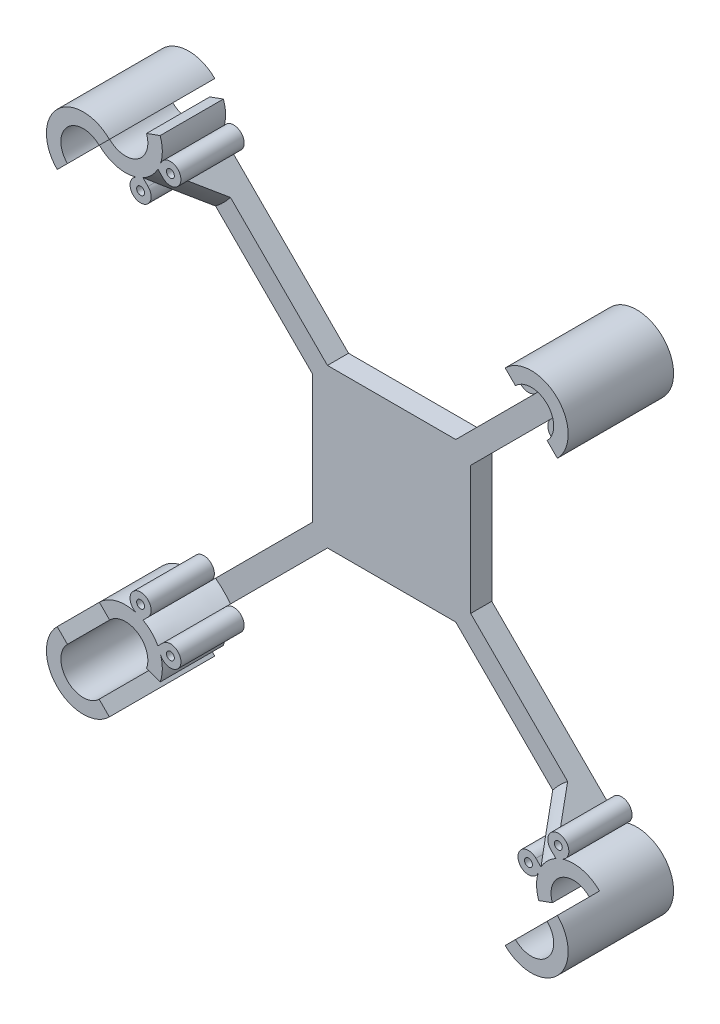
SolidWorks part; units mm, degrees
material "ABS"
ref_plane "Plano frontal" through (0, 0, 0) normal (0, 0, 1) x (1, 0, 0)
ref_plane "Plano superior" through (0, 0, 0) normal (0, 1, 0) x (1, 0, 0)
ref_plane "Plano direito" through (0, 0, 0) normal (1, 0, 0) x (0, 0, -1)
sketch "Esboço1" plane through (0, 0, 0) normal (0, 0, 1) x (1, 0, 0)
  line L0 (0, 0) -> (42.5, 42.5) construction
  line L1 (38.5063, 43.9536) -> (35.9222, 44.8941)
  line L2 (12.1716, 15) -> (36.3424, 39.1708)
  line L3 (-12.1716, 15) -> (12.1716, 15)
  line L4 (15, -12.1716) -> (15, 12.1716)
  line L5 (-1.4142, 1.4142) -> (41.0858, 43.9142) construction
  line L6 (0, 0) -> (-42.5, 42.5) construction
  line L7 (0, -45.0528) -> (0, 45.0528) construction
  line L8 (-57.1727, 0) -> (57.1727, 0) construction
  line L9 (15, 12.1716) -> (39.1708, 36.3424)
  line L10 (37.5503, 47.4497) -> (39.4948, 45.5052)
  line L11 (-37.5503, 47.4497) -> (-39.4948, 45.5052)
  line L12 (-15, 12.1716) -> (-39.1708, 36.3424)
  line L13 (-15, -12.1716) -> (-15, 12.1716)
  line L14 (-12.1716, 15) -> (-36.3424, 39.1708)
  line L15 (-38.5063, 43.9536) -> (-35.9222, 44.8941)
  line L16 (0, 0) -> (-42.5, -42.5) construction
  line L17 (0, 0) -> (42.5, -42.5) construction
  line L18 (-38.5063, -43.9536) -> (-35.9222, -44.8941)
  line L19 (-12.1716, -15) -> (-36.3424, -39.1708)
  line L20 (-15, -12.1716) -> (-39.1708, -36.3424)
  line L21 (-37.5503, -47.4497) -> (-39.4948, -45.5052)
  line L22 (37.5503, -47.4497) -> (39.4948, -45.5052)
  line L23 (15, -12.1716) -> (39.1708, -36.3424)
  line L24 (-12.1716, -15) -> (12.1716, -15)
  line L25 (12.1716, -15) -> (36.3424, -39.1708)
  line L26 (38.5063, -43.9536) -> (35.9222, -44.8941)
  line L27 (42.5, 42.5) -> (31.5501, 42.5) construction
  arc A0 (38.5063, 43.9536) -> (39.4948, 45.5052) centre (42.5, 42.5) ccw
  arc A1 (36.3424, 39.1708) -> (37.5503, 47.4497) centre (42.5, 42.5) ccw
  arc A2 (35.9222, 44.8941) -> (36.3424, 39.1708) centre (42.5, 42.5) ccw
  arc A3 (-35.9222, 44.8941) -> (-36.3424, 39.1708) centre (-42.5, 42.5) cw
  arc A4 (-36.3424, 39.1708) -> (-37.5503, 47.4497) centre (-42.5, 42.5) cw
  arc A5 (-38.5063, 43.9536) -> (-39.4948, 45.5052) centre (-42.5, 42.5) cw
  arc A6 (-38.5063, -43.9536) -> (-39.4948, -45.5052) centre (-42.5, -42.5) ccw
  arc A7 (-36.3424, -39.1708) -> (-37.5503, -47.4497) centre (-42.5, -42.5) ccw
  arc A8 (-35.9222, -44.8941) -> (-36.3424, -39.1708) centre (-42.5, -42.5) ccw
  arc A9 (35.9222, -44.8941) -> (36.3424, -39.1708) centre (42.5, -42.5) cw
  arc A10 (36.3424, -39.1708) -> (37.5503, -47.4497) centre (42.5, -42.5) cw
  arc A11 (38.5063, -43.9536) -> (39.4948, -45.5052) centre (42.5, -42.5) cw
  point P0 (0, 0)
  point P29 (0, 15)
  point P46 (-15, 0)
  point P47 (15, 0)
  point P48 (0, -15)
  dimension "D2" = 14
  dimension "D3" = 8.5
  dimension "D1" = 30
  dimension "D4" = 85
  dimension "D5" = 30
  dimension "D7" = 45
  dimension "D8" = 25
  dimension "D9" = 2
  dimension "D10" = 20
  dimension "D6" = 2
extrude "Ressalto-extrusão1" add sketch "Esboço1" along normal blind 4 contours L25 A10 L23 L4 L9 A1 L2 L3 L14 A4 L12 L13 L20 A7 L19 L24 region at (0, 0, 0)
extrude "Ressalto-extrusão2" add sketch "Esboço1<4>" along normal blind 20 contours L15 A5 L11 A4 A3 | A1 L10 A0 L1 A2 | A9 L26 A11 L22 A10 | A8 L18 A6 L21 A7 region at (-37.6903, 37.6903, 0)
sketch "Esboço1<4>" plane through (0, 0, 0) normal (0, 0, 1) x (1, 0, 0) same geometry as "Esboço1"
chamfer "Chanfro1" distance 8 angle 45 4 edges at (37.5503, -37.5503, 4) (37.5503, 37.5503, 4) (-37.5503, 37.5503, 4) (-37.5503, -37.5503, 4)
sketch "Esboço2" plane through (0, 0, 20) normal (0, 0, 1) x (1, 0, 0)
  line L0 (85, 0) -> (0, 85)
  line L1 (85, 0) -> (0, -85)
  line L2 (0, 85) -> (-85, 0)
  line L3 (0, -85) -> (-85, 0)
  line L4 (85, 0) -> (-85, 0) construction
  line L5 (0, 85) -> (0, -85) construction
  arc A0 (-39.4948, 45.5052) -> (-38.5063, 43.9536) centre (-42.5, 42.5) ccw construction
  arc A1 (-38.5063, -43.9536) -> (-39.4948, -45.5052) centre (-42.5, -42.5) ccw construction
  point P1 (0, 0)
  point P11 (-42.5, 42.5)
  point P12 (-42.5, -42.5)
extrude "Corte-extrusão1" cut sketch "Esboço2" against normal blind 8
sketch "Esboço3" plane through (0, 0, 0) normal (0, 0, -1) x (-1, 0, 0)
  line L0 (15, 12.1716) -> (39.1708, 36.3424) construction
  line L2 (38.2133, 35.3849) -> (39.1708, 36.3424)
  line L3 (37.2779, 37.2779) -> (34.8393, 34.8393) construction
  line L4 (33.4251, 36.2535) -> (36.2535, 33.4251) construction
  line L5 (12.1716, 15) -> (36.3424, 39.1708) construction
  line L6 (35.3849, 38.2133) -> (36.3424, 39.1708)
  line L7 (35.3849, -38.2133) -> (36.3424, -39.1708)
  line L8 (38.2133, -35.3849) -> (39.1708, -36.3424)
  line L9 (-38.2133, -35.3849) -> (-39.1708, -36.3424)
  line L10 (-35.3849, -38.2133) -> (-36.3424, -39.1708)
  line L11 (-35.3849, 38.2133) -> (-36.3424, 39.1708)
  line L12 (-38.2133, 35.3849) -> (-39.1708, 36.3424)
  arc A0 (38.2133, 35.3849) -> (40.2659, 35.8661) centre (39.6275, 33.9707) ccw
  arc A1 (39.1708, 36.3424) -> (37.5503, 47.4497) centre (42.5, 42.5) ccw construction
  circle A2 centre (39.6275, 33.9707) radius 0.75
  arc A4 (39.1708, 36.3424) -> (40.2659, 35.8661) centre (42.5, 42.5) ccw
  arc A5 (36.3424, 39.1708) -> (35.8661, 40.2659) centre (42.5, 42.5) cw
  circle A6 centre (33.9707, 39.6275) radius 0.75
  arc A7 (35.3849, 38.2133) -> (35.8661, 40.2659) centre (33.9707, 39.6275) cw
  arc A8 (35.3849, -38.2133) -> (35.8661, -40.2659) centre (33.9707, -39.6275) ccw
  circle A9 centre (33.9707, -39.6275) radius 0.75
  arc A10 (36.3424, -39.1708) -> (35.8661, -40.2659) centre (42.5, -42.5) ccw
  arc A11 (39.1708, -36.3424) -> (40.2659, -35.8661) centre (42.5, -42.5) cw
  circle A12 centre (39.6275, -33.9707) radius 0.75
  arc A13 (38.2133, -35.3849) -> (40.2659, -35.8661) centre (39.6275, -33.9707) cw
  arc A14 (-38.2133, -35.3849) -> (-40.2659, -35.8661) centre (-39.6275, -33.9707) ccw
  circle A15 centre (-39.6275, -33.9707) radius 0.75
  arc A16 (-39.1708, -36.3424) -> (-40.2659, -35.8661) centre (-42.5, -42.5) ccw
  arc A17 (-36.3424, -39.1708) -> (-35.8661, -40.2659) centre (-42.5, -42.5) cw
  circle A18 centre (-33.9707, -39.6275) radius 0.75
  arc A19 (-35.3849, -38.2133) -> (-35.8661, -40.2659) centre (-33.9707, -39.6275) cw
  arc A20 (-35.3849, 38.2133) -> (-35.8661, 40.2659) centre (-33.9707, 39.6275) ccw
  circle A21 centre (-33.9707, 39.6275) radius 0.75
  arc A22 (-36.3424, 39.1708) -> (-35.8661, 40.2659) centre (-42.5, 42.5) ccw
  arc A23 (-39.1708, 36.3424) -> (-40.2659, 35.8661) centre (-42.5, 42.5) cw
  circle A24 centre (-39.6275, 33.9707) radius 0.75
  arc A25 (-38.2133, 35.3849) -> (-40.2659, 35.8661) centre (-39.6275, 33.9707) cw
  point P55 (0, 0)
  dimension "D1" = 4
  dimension "D2" = 1.5
  dimension "D3" = 4
extrude "Ressalto-extrusão3" add sketch "Esboço3" against normal up to surface (12 mm away) up to face at (-40.0813, 39.4955, 12)
